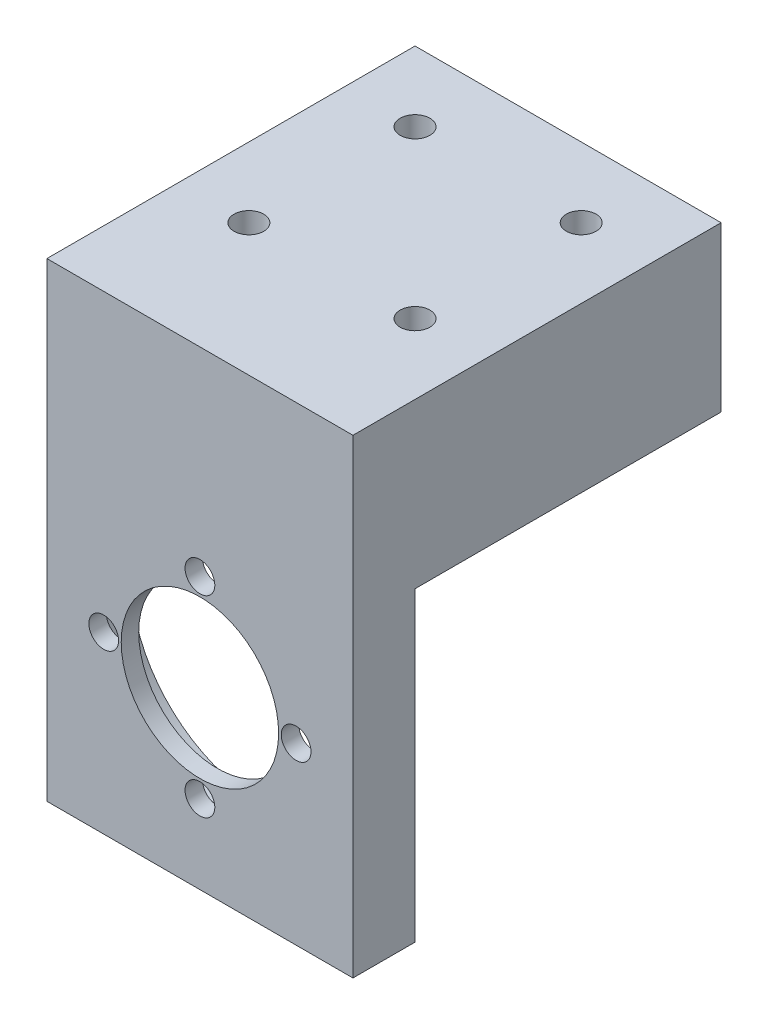
SolidWorks part; units mm, degrees
material "PET"
ref_plane "Front Plane" through (0, 0, 0) normal (0, 0, 1) x (1, 0, 0)
ref_plane "Top Plane" through (0, 0, 0) normal (0, 1, 0) x (1, 0, 0)
ref_plane "Right Plane" through (0, 0, 0) normal (1, 0, 0) x (0, 0, -1)
sketch "Sketch1" plane through (0, 0, 0) normal (1, 0, 0) x (0, 0, -1)
  line L0 (0, 0) -> (7.1, 0)
  line L1 (7.1, 0) -> (7.1, 35)
  line L2 (7.1, 35) -> (42.1, 35)
  line L3 (42.1, 35) -> (42.1, 53.75)
  line L4 (42.1, 53.75) -> (0, 53.75)
  line L5 (0, 53.75) -> (0, 0)
  dimension "D1" = 35
  dimension "D2" = 18.75
  dimension "D3" = 7.1
  dimension "D4" = 35
extrude "Boss-Extrude1" add sketch "Sketch1" along normal blind 35
sketch "Sketch2" plane through (0, 0, 0) normal (0, 0, 1) x (1, 0, 0)
  line L0 (35, 0) -> (0, 0) construction
  line L9 (17.5, 0) -> (17.5, 39.0737) construction
  line L10 (0, 0) -> (0, 35) construction
  circle A0 centre (17.5, 20) radius 15
  circle A1 centre (17.5, 20) radius 11 construction
  circle A2 centre (17.5, 31) radius 1.7
  circle A3 centre (28.5, 20) radius 1.7
  circle A4 centre (17.5, 9) radius 1.7
  circle A5 centre (6.5, 20) radius 1.7
  circle A6 centre (17.5, 20) radius 9
  dimension "D1" = 30
  dimension "D2" = 22
  dimension "D3" = 3.4
  dimension "D5" = 18
  dimension "D6" = 20
  dimension "D7" = 17.5
  dimension "D4" = 4
extrude "Motor mount bolt holes" cut sketch "Sketch2" along direction (0, 0, -1) on the side of the normal up to surface and the other way up to surface (42.1 mm away) from surface contours A5 | A4 | A3 | A2 | A6 up to face at (17.5, 26.875, 0) other way up to face at (17.5, 44.375, -42.1) starting at face at (17.5, 17.5, -7.1)
extrude "Motor Countersink" cut sketch "Sketch2<5>" along normal blind 5.1 and the other way up to surface (42.1 mm away) from surface contours A6 A2 A0 A4 A5 | A6 A4 A0 A2 A3 region at (2.9243, 20, 0) other way up to face at (17.5, 44.375, -42.1) starting at face at (8.2, 20, -7.1)
sketch "Sketch2<5>" plane through (0, 0, 0) normal (0, 0, 1) x (1, 0, 0) same geometry as "Sketch2"
sketch "Sketch3" plane through (0, 35, 0) normal (0, -1, 0) x (1, 0, 0)
  line L0 (17.5, 0) -> (17.5, -42.1) construction
  line L1 (35, 0) -> (0, 0) construction
  line L2 (35, -42.1) -> (0, -42.1) construction
  line L3 (0, -7.1) -> (0, -42.1) construction
  line L4 (17.5, -7.1) -> (0, -7.1) construction
  line L5 (0, -24.6) -> (35, -24.6) construction
  line L6 (35, -7.1) -> (35, -42.1) construction
  circle A0 centre (8, -15.1) radius 1.7
  circle A1 centre (27, -15.1) radius 1.7
  circle A2 centre (27, -34.1) radius 1.7
  circle A3 centre (8, -34.1) radius 1.7
  dimension "D1" = 3.4
  dimension "D2" = 8
  dimension "D3" = 8
extrude "Cut-Extrude3" cut sketch "Sketch3" against normal through all
equation "\"h\"= 35"
equation "\"w\"= 35"
equation "\"t1\"=7.1"
equation "\"D1@Sketch1\"=\"h\""
equation "\"D2@Sketch1\"=\"t2\""
equation "\"D3@Sketch1\"=\"t1\""
equation "\"D1@Boss-Extrude1\"=\"w\""
equation "\"D4@Sketch1\"=\"w\""
equation "\"t2\"= 18.75"
equation "\"bolt hole dia\"= 3.4"
equation "\"D1@Sketch3\"=\"bolt hole dia\""
